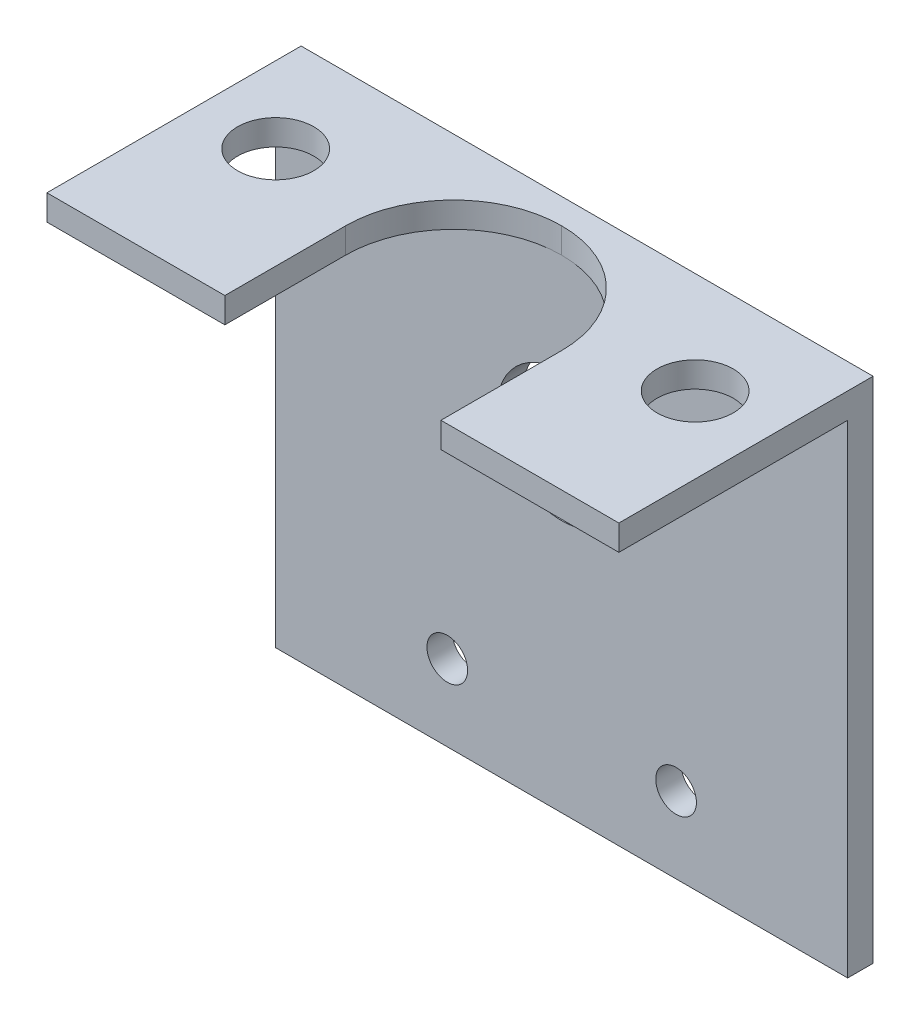
SolidWorks part; units mm, degrees
ref_plane "正面" through (0, 0, 0) normal (0, 0, 1) x (1, 0, 0)
ref_plane "平面" through (0, 0, 0) normal (0, 1, 0) x (1, 0, 0)
ref_plane "右側面" through (0, 0, 0) normal (1, 0, 0) x (0, 0, -1)
sketch "ｽｹｯﾁ1" plane through (0, 0, 0) normal (1, 0, 0) x (0, 0, -1)
  line L0 (-18, 40) -> (-18, 38)
  line L1 (-18, 38) -> (0, 38)
  line L2 (0, 38) -> (0, 0)
  line L3 (0, 0) -> (2, 0)
  line L4 (2, 0) -> (2, 40)
  line L5 (2, 40) -> (-18, 40)
  dimension "D1" = 20
  dimension "D2" = 40
  dimension "D3" = 2
  dimension "D4" = 2
extrude "ﾎﾞｽ - 押し出し1" add sketch "ｽｹｯﾁ1" along normal blind 45
sketch "ｽｹｯﾁ2" plane through (0, 0, 0) normal (0, 0, 1) x (1, 0, 0)
  line L0 (0, 38) -> (45, 12) construction
  line L1 (45, 38) -> (0, 12) construction
  line L2 (45, 38) -> (45, 0) construction
  line L3 (0, 12) -> (45, 12) construction
  line L4 (0, 12) -> (0, 0) construction
  line L5 (0, 0) -> (45, 0) construction
  line L6 (45, 12) -> (45, 0) construction
  line L7 (0, 12) -> (45, 0) construction
  line L8 (0, 0) -> (45, 12) construction
  line L9 (0, 6) -> (45, 6) construction
  circle A0 centre (22.5, 25) radius 5.1
  circle A1 centre (13.5, 6) radius 1.6
  circle A2 centre (31.5, 6) radius 1.6
  point P11 (22.5, 25)
  point P17 (22.5, 6)
  dimension "D1" = 10.2
  dimension "D3" = 3.2
  dimension "D4" = 3.2
  dimension "D2" = 12
  dimension "D5" = 13.5
  dimension "D6" = 13.5
extrude "ｶｯﾄ - 押し出し1" cut sketch "ｽｹｯﾁ2" against normal through all
sketch "ｽｹｯﾁ3" plane through (0, 38, 0) normal (0, -1, 0) x (1, 0, 0)
  line L0 (0, 6) -> (45, 6) construction
  line L1 (0, 18) -> (0, 0) construction
  line L2 (45, 18) -> (45, 0) construction
  line L3 (45, 18) -> (0, 18) construction
  line L4 (14, 18) -> (31, 18)
  line L5 (14, 18) -> (14, 0)
  line L6 (14, 0) -> (31, 0)
  line L7 (31, 18) -> (31, 0)
  line L8 (14, 18) -> (31, 0) construction
  line L9 (14, 0) -> (31, 18) construction
  line L10 (45, 0) -> (0, 0) construction
  line L11 (45, 18) -> (0, 18) construction
  line L12 (0, 9) -> (45, 9) construction
  line L13 (22.5, 18) -> (22.5, 0) construction
  circle A0 centre (6, 6) radius 3
  circle A1 centre (39, 6) radius 3
  point P19 (22.5, 9)
  dimension "D1" = 6
  dimension "D2" = 6
  dimension "D3" = 6
  dimension "D4" = 17
  dimension "D5" = 6
extrude "ｶｯﾄ - 押し出し2" cut sketch "ｽｹｯﾁ3" against normal through all
fillet "ﾌｨﾚｯﾄ1" radius 8.5 2 edges at (31, 39, 0) (14, 39, 0)
